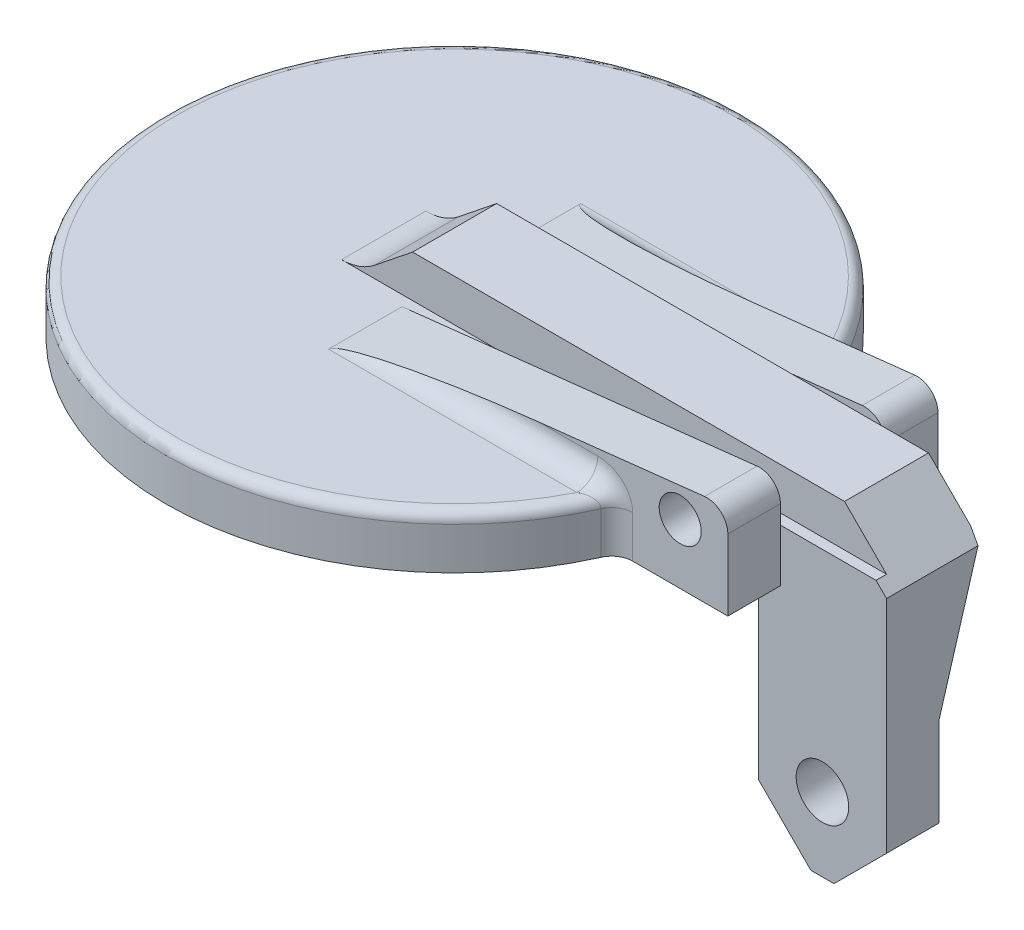
SolidWorks part; units mm, degrees
ref_plane "Front Plane" through (0, 0, 0) normal (0, 0, 1) x (1, 0, 0)
ref_plane "Top Plane" through (0, 0, 0) normal (0, 1, 0) x (1, 0, 0)
ref_plane "Right Plane" through (0, 0, 0) normal (1, 0, 0) x (0, 0, -1)
sketch "Sketch2" plane through (0, 0, 0) normal (0, 0, 1) x (1, 0, 0)
  line L3 (27.5, 5) -> (27.5, 10)
  line L4 (27.5, 10) -> (0, 10)
  line L5 (0, 10) -> (0, 5)
  line L7 (0, 0) -> (0, 5) construction
  line L8 (0, 5) -> (27.5, 5)
  dimension "D1" = 27.5
  dimension "D2" = 5
  dimension "D4" = 5
revolve "Revolve1" add sketch "Sketch2" angle 360 about L5
fillet "Fillet1" radius 1 1 edges at (0, 10, 27.5)
sketch "Sketch5" plane through (0, 0, 0) normal (0, 0, 1) x (1, 0, 0)
  line L4 (0, 10) -> (46.1, 10)
  line L5 (26.5, 10) -> (-26.5, 10) construction
  line L6 (0, 14) -> (46.1, 14)
  line L7 (46.1, 14) -> (46.1, 10)
  line L8 (0, 10) -> (-5, 10)
  line L9 (-5, 10) -> (0, 14)
  dimension "D3" = 5
  dimension "D1" = 46.1
  dimension "D2" = 4
  dimension "D4" = 6.4031
extrude "Boss-Extrude2" add sketch "Sketch5" along normal mid plane 8
sketch "Sketch14" plane through (0, 0, 0) normal (0, 0, 1) x (1, 0, 0)
  line L5 (46.1, 10) -> (33.9, 10)
  line L6 (26.1964, 10) -> (46.1, 10) construction
  line L7 (33.9, 10) -> (33.9, -17)
  line L8 (33.9, -17) -> (46.1, -17)
  line L9 (46.1, -17) -> (46.1, 10)
  line L10 (40, -17) -> (40, -10) construction
  circle A0 centre (40, -10) radius 2.5
  dimension "D2" = 5
  dimension "D1" = 7
  dimension "D3" = 12.2
  dimension "D4" = 27
extrude "Boss-Extrude6" add sketch "Sketch14" along normal blind 5
sketch "Sketch15" plane through (46.1, 0, 0) normal (1, 0, 0) x (0, 0, -1)
  line L0 (4, 10) -> (0, -3.5)
  line L1 (0, -17) -> (0, 10) construction
  line L2 (4, 10) -> (0, 10)
  line L3 (0, 10) -> (0, -3.5)
extrude "Boss-Extrude7" add sketch "Sketch15" against normal blind 12.2
fillet "Fillet2" radius 5 1 edges at (-5, 10, 0)
chamfer "Chamfer1" distance 5 angle 45 3 edges at (46.1, 14, 0) (33.9, -17, 2.5) (46.1, -17, 2.5)
sketch "Sketch17" plane through (0, 0, 0) normal (0, 0, 1) x (1, 0, 0)
  line L0 (0, 5) -> (36, 5)
  line L1 (-27.5, 5) -> (27.5, 5) construction
  line L2 (0, 5) -> (0, 10)
  line L3 (26.1964, 10) -> (-26.5, 10) construction
  line L4 (0, 10) -> (36, 14)
  line L5 (41.1, 14) -> (0, 14) construction
  line L6 (36, 14) -> (36, 5)
  dimension "D1" = 36
extrude "Boss-Extrude8" add sketch "Sketch17" along normal blind 5 from offset 5
sketch "Sketch21" plane through (0, 0, 0) normal (0, 1, 0) x (1, 0, 0)
  line L0 (30, 0) -> (52.5, 0)
  line L1 (52.5, -10) -> (52.5, 10) construction
  line L2 (52.5, 10) -> (36.1421, 10) construction
  line L3 (52.5, -10) -> (36.1421, -10) construction
  line L4 (28.2843, 10) -> (34.8065, 10)
  line L5 (28.2843, 10) -> (28.2843, 13.9557)
  line L6 (28.2843, 13.9557) -> (34.8065, 13.9557)
  line L7 (34.8065, 13.9557) -> (34.8065, 10)
  circle A0 centre (0, 0) radius 30
  circle A1 centre (0, 0) radius 37.5
  point P9 (52.5, 0)
  dimension "D1" = 60
  dimension "D2" = 75
  dimension "D3" = 22.5
  dimension "D4" = 20
  dimension "D5" = 3.9556
  dimension "D6" = 6.5222
sketch "Sketch22" plane through (0, 0, 10) normal (0, 0, 1) x (1, 0, 0)
  line L0 (25.6174, 5) -> (28.2174, 5) construction
  line L2 (25.6174, 5) -> (36, 5) construction
  line L3 (28.2174, 5) -> (31.4674, 5) construction
  line L4 (31.4674, 5) -> (31.4674, 10.7) construction
  circle A0 centre (31.4674, 10.7) radius 2
  dimension "D4" = 4
  dimension "D1" = 2.6
  dimension "D2" = 3.25
  dimension "D3" = 5.7
extrude "Cut-Extrude1" cut sketch "Sketch22" against normal blind 5
fillet "Fillet6" radius 2 4 edges at (25.6174, 7, 10) (25.4154, 9.5838, 10) (36, 14, 7.5) (12.2704, 10, 10)
mirror "Mirror3" about plane through (0, 0, 0) normal (0, 0, 1) of "Fillet6", "Cut-Extrude1", "Boss-Extrude8"
